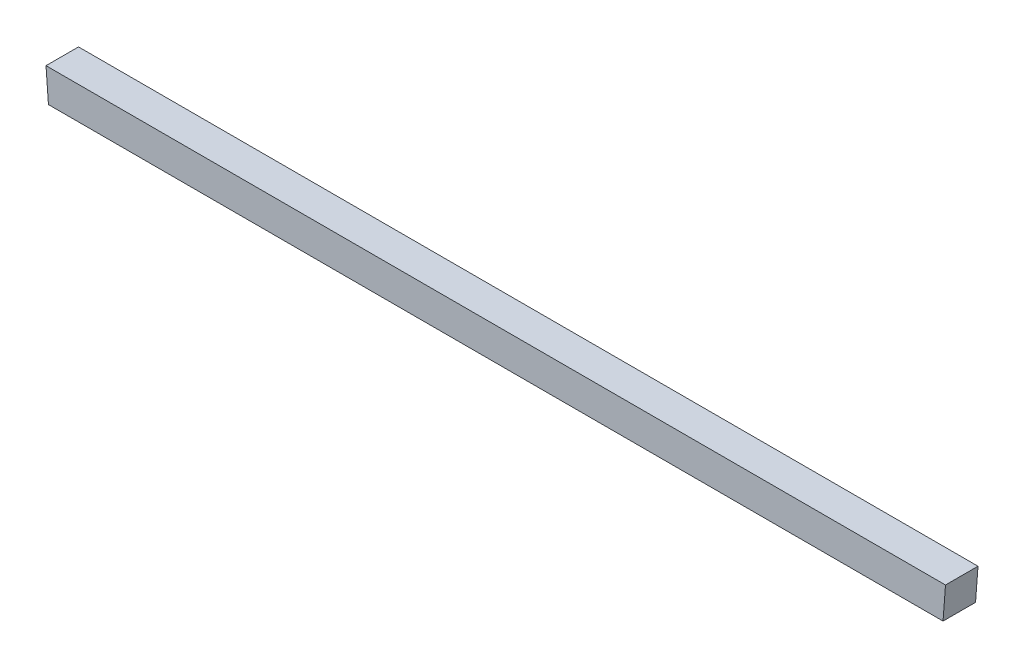
SolidWorks part; units mm, degrees
ref_plane "Front Plane" through (0, 0, 0) normal (0, 0, 1) x (1, 0, 0)
ref_plane "Top Plane" through (0, 0, 0) normal (0, 1, 0) x (1, 0, 0)
ref_plane "Right Plane" through (0, 0, 0) normal (1, 0, 0) x (0, 0, -1)
sketch "Sketch1" plane through (0, 0, 0) normal (0, 0, 1) x (1, 0, 0)
  line L5 (-4150, 150) -> (-4300, 150)
  line L6 (-4150, -150) -> (4150, -150)
  line L11 (-4150, -150) -> (-4150, 150)
  line L12 (-4150, 150) -> (4150, 150)
  line L13 (0, -150) -> (0, 150)
  line L14 (-4150, -150) -> (0, 150) construction
  line L15 (-4150, 150) -> (0, -150) construction
  line L16 (-4300, 150) -> (-4300, -1850)
  line L17 (-4150, 150) -> (-4000, -1850)
  line L18 (-4000, -1850) -> (-4300, -1850)
  line L19 (4150, 150) -> (4000, -1850)
  point P0 (-2075, 0)
  dimension "D1" = 300
  dimension "D2" = 4150
  dimension "D3" = 2000
  dimension "D4" = 150
  dimension "D5" = 300
extrude "Boss-Extrude1" add sketch "Sketch1" along normal blind 150 and the other way blind 150 contours L12 L17 L6 L13 | L19 L12 L13 L6 region at (-2069.3801, 0.1359, 0) region at (2069.3801, 0.1359, 0)
